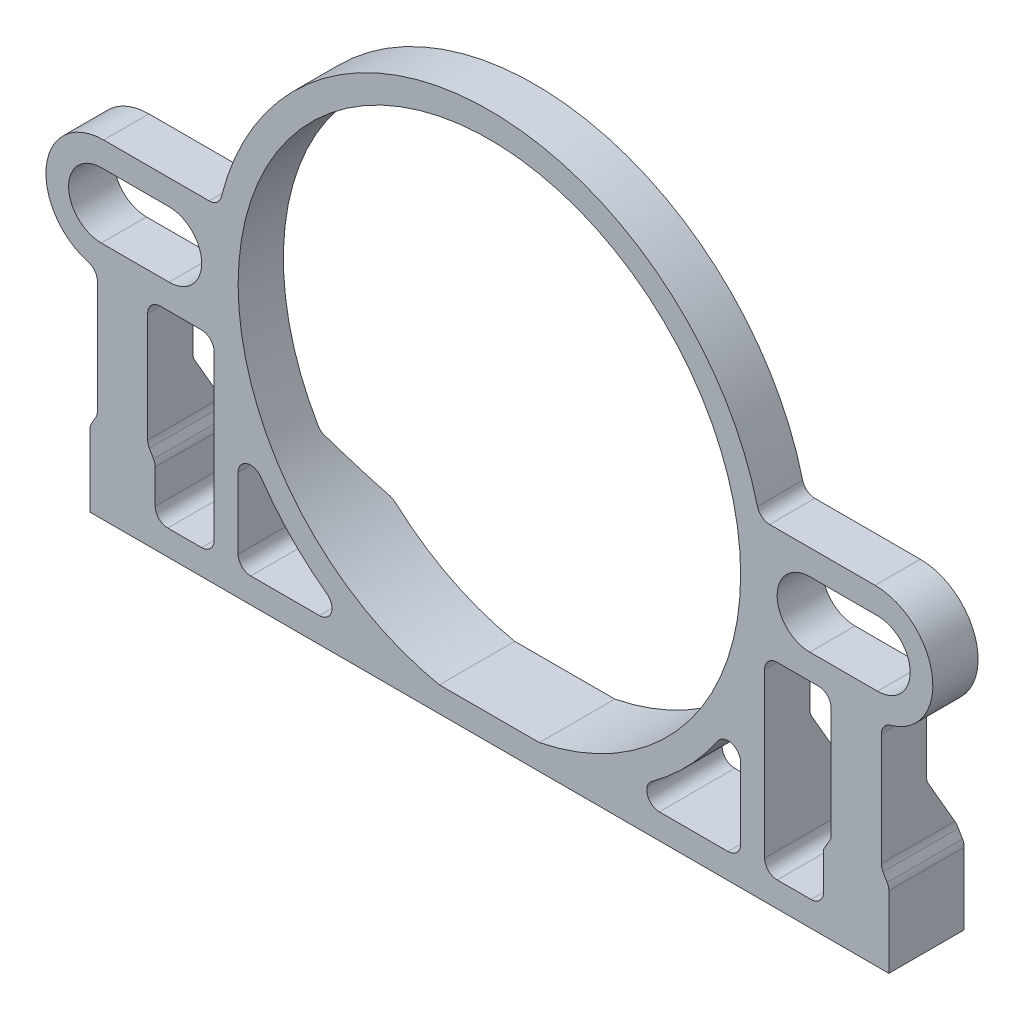
SolidWorks part; units mm, degrees
ref_plane "前视基准面" through (0, 0, 0) normal (0, 0, 1) x (1, 0, 0)
ref_plane "上视基准面" through (0, 0, 0) normal (0, 1, 0) x (1, 0, 0)
ref_plane "右视基准面" through (0, 0, 0) normal (1, 0, 0) x (0, 0, -1)
sketch "草图1" plane through (0, 0, 0) normal (0, 0, 1) x (1, 0, 0)
  line L1 (15.6, -6) -> (-15.6, -6)
  line L2 (15.6, -6) -> (15.6, 6)
  line L3 (15.6, 6) -> (-15.6, 6)
  line L4 (-15.6, -6) -> (-15.6, 6)
  line L5 (15.6, -6) -> (-15.6, 6) construction
  line L6 (15.6, 6) -> (-15.6, -6) construction
  point P0 (0, 0)
  dimension "D1" = 31.2
  dimension "D2" = 12
extrude "凸台-拉伸1" add sketch "草图1" along normal blind 3
sketch "草图2" plane through (0, 0, 3) normal (0, 0, 1) x (1, 0, 0)
  line L0 (15.6, 6) -> (-15.6, 6) construction
  line L1 (-13.6, 6) -> (13.6, 6)
  line L2 (-13.6, 6) -> (-13.6, -5)
  line L3 (-13.6, -5) -> (13.6, -5)
  line L4 (13.6, 6) -> (13.6, -5)
  line L5 (-15.6, 6) -> (-15.6, -6) construction
  line L6 (-15.6, -6) -> (15.6, -6) construction
  dimension "D1" = 2
  dimension "D2" = 27.2
  dimension "D3" = 1
extrude "切除-拉伸1" cut sketch "草图2" against normal blind 3
sketch "草图3" plane through (0, 0, 3) normal (0, 0, 1) x (1, 0, 0)
  line L0 (-15.6, -6) -> (15.6, -6) construction
  line L1 (0, 0) -> (0, 50000) construction
  line L2 (-15.6, 6) -> (-15.6, -6) construction
  circle A0 centre (-14.6, 4.8) radius 2.25
  circle A1 centre (14.6, 4.8) radius 2.25
  dimension "D1" = 10.8
  dimension "D2" = 1
extrude "凸台-拉伸2" add sketch "草图3" against normal blind 3
sketch "草图4" plane through (0, 0, 3) normal (0, 0, 1) x (1, 0, 0)
  circle A0 centre (-14.6, 4.8) radius 1.3
  circle A1 centre (14.6, 4.8) radius 1.3
extrude "切除-拉伸2" cut sketch "草图4" against normal blind 3
sketch "草图5" plane through (0, 0, 3) normal (0, 0, 1) x (1, 0, 0)
  line L0 (-15.6, 2.7844) -> (-15.6, -6) construction
  line L1 (-15.6, -6) -> (15.6, -6) construction
  line L2 (0, 0) -> (0, 50000) construction
  circle A0 centre (-14.6, -2) radius 2.25
  circle A1 centre (14.6, -2) radius 2.25
  dimension "D1" = 1
  dimension "D2" = 4
sketch "草图8" plane through (0, 0, 0) normal (0, 0, -1) x (-1, 0, 0)
  line L0 (-14.6, 4.8) -> (14.6, 4.8) construction
  line L1 (-12.5844, 5.8) -> (-10.9545, 5.8)
  line L2 (-12.5844, 3.8) -> (-10.9545, 3.8)
  line L3 (-10.9545, 3.8) -> (-9.9499, 3.8)
  line L4 (0, 4.8) -> (0, 50004.8) construction
  line L5 (10.9545, 3.8) -> (9.9499, 3.8)
  line L6 (12.5844, 3.8) -> (10.9545, 3.8)
  line L7 (12.5844, 5.8) -> (10.9545, 5.8)
  circle A0 centre (0, 4.8) radius 9 construction
  circle A1 centre (0, 4.8) radius 11 construction
  arc A2 (-13.6, 2.7844) -> (-15.6, 2.7844) centre (-14.6, 4.8) ccw construction
  arc A3 (-10.9545, 5.8) -> (10.9545, 5.8) centre (0, 4.8) cw
  circle A4 centre (0, 4.8) radius 10 construction
  arc A5 (-9.9499, 3.8) -> (9.9499, 3.8) centre (0, 4.8) cw
  arc A6 (-12.5844, 5.8) -> (-12.5844, 3.8) centre (-14.6, 4.8) cw
  arc A7 (12.5844, 5.8) -> (12.5844, 3.8) centre (14.6, 4.8) ccw
  dimension "D1" = 1
  dimension "D2" = 1
extrude "凸台-拉伸5" add sketch "草图8" against normal blind 3
fillet "圆角2" radius 1 6 edges at (-12.5844, 5.8, 1.5) (-10.9545, 5.8, 1.5) (12.5844, 5.8, 1.5) (10.9545, 5.8, 1.5) (-9.9499, 3.8, 1.5) (9.9499, 3.8, 1.5)
sketch "草图9" plane through (0, -6, 0) normal (0, -1, 0) x (-1, 0, 0)
  line L0 (-14.6, 0) -> (14.6, 0) construction
  line L1 (13.5896, -3) -> (15.6104, -3)
  line L3 (16.6207, -1.25) -> (15.6104, 0.5)
  line L4 (15.6104, 0.5) -> (13.5896, 0.5)
  line L5 (13.5896, 0.5) -> (12.5844, -1.2411)
  line L7 (15.6, -3) -> (15.6, 0) construction
  line L8 (-12.5844, -1.2411) -> (-12.5844, -3)
  line L9 (15.6, -3) -> (-15.6, -3) construction
  line L10 (0, 0) -> (0, 7.3942) construction
  line L12 (-13.5896, 0.5) -> (-12.5844, -1.2411)
  line L13 (-15.6104, 0.5) -> (-13.5896, 0.5)
  line L14 (-16.6207, -1.25) -> (-15.6104, 0.5)
  line L16 (-13.5896, -3) -> (-15.6104, -3)
  line L17 (-12.5844, -3) -> (-13.5896, -3)
  line L18 (12.5844, -1.2411) -> (12.5844, -3)
  line L19 (12.5844, -3) -> (13.5896, -3)
  line L20 (-16.6207, -1.25) -> (-16.6207, -3)
  line L21 (12.5793, -1.25) -> (13.5896, -3) [skipped]
  line L22 (-16.85, -3) -> (-12.8265, -3) construction
  line L23 (-16.6207, -3) -> (-15.6104, -3)
  line L24 (16.6207, -1.25) -> (16.6207, -3)
  line L25 (12.8265, -3) -> (16.85, -3) construction
  line L26 (16.6207, -3) -> (15.6104, -3)
  line L28 (15.6104, -3) -> (16.6207, -1.25) [skipped]
  circle A0 centre (14.6, -1.25) radius 1.75 construction
  circle A1 centre (14.6, -1.25) radius 1.05 construction
  circle A2 centre (-14.6, -1.25) radius 1.05 construction
  dimension "D3" = 1.25
  dimension "D1" = 1
  dimension "D2" = 3.5
extrude "凸台-拉伸6" add sketch "草图9" against normal blind 3.5
sketch "草图12" plane through (0, 0, 0) normal (0, 0, -1) x (-1, 0, 0)
  line L0 (-10.9545, 3.8) -> (-10.9545, -5)
  line L1 (13.301, -5) -> (-13.301, -5) construction
  line L2 (-10, 4.8) -> (-10, -5)
  line L3 (-10, -5) -> (-10.9545, -5)
  line L4 (-10.9545, 3.8) -> (-10.9545, 4.8)
  line L5 (-14.6, 4.8) -> (14.6, 4.8) construction
  line L6 (-10.9545, 4.8) -> (-10, 4.8)
  line L7 (0, 4.8) -> (0, 50004.8) construction
  line L9 (10.9545, 3.8) -> (10.9545, 4.8)
  line L10 (10.9545, 3.8) -> (10.9545, -5)
  line L11 (10, -5) -> (10.9545, -5)
  line L12 (10, 4.8) -> (10, -5)
  line L13 (10.9545, 4.8) -> (10, 4.8)
extrude "凸台-拉伸8" add sketch "草图12" against normal blind 3
fillet "圆角3" radius 0.5 10 edges at (10.9545, -5, 1.5) (13.6, 2.7844, 1.5) (12.5844, 3.8, 1.5) (10.9545, 3.801, 1.5) (-13.6, 2.7844, 1.5) (-12.5844, 3.8, 1.5) (-10.9545, 3.801, 1.5) (-10.9545, -5, 1.5) (-10, -5, 1.5) (10, -5, 1.5)
sketch "草图13" plane through (0, 0, 0) normal (0, 0, -1) x (-1, 0, 0)
  line L0 (-10, -4.5) -> (-10, 4.8) construction
  line L1 (9.5, -5) -> (-9.5, -5) construction
  line L2 (-4.9565, -5.02) -> (-1.8886, -5.02)
  line L3 (1.99, -5) -> (4.996, -5)
  line L4 (10, 0.2174) -> (10, 4.8)
  line L5 (-10, 4.8) -> (-10, 0.2174)
  arc A0 (-10, 0.2174) -> (-4.9565, -5.02) centre (0, 4.8) ccw
  circle A1 centre (0, 4.8) radius 11 construction
  arc A2 (-1.8886, -5.02) -> (-10, 4.8) centre (0, 4.8) cw
  circle A3 centre (0, 4.8) radius 10 construction
  arc A4 (9.9499, 3.8) -> (-9.9499, 3.8) centre (0, 4.8) ccw construction
  arc A5 (1.99, -5) -> (10, 4.8) centre (0, 4.8) ccw
  arc A6 (10, 0.2174) -> (4.996, -5) centre (0, 4.8) cw
extrude "凸台-拉伸9" add sketch "草图13" against normal blind 3
fillet "圆角4" radius 0.5 4 edges at (-10, 0.2174, 1.5) (-4.996, -5, 1.5) (4.996, -5, 1.5) (10, 0.2174, 1.5)
sketch "草图14" plane through (0, -2.5, 0) normal (0, 1, 0) x (1, 0, 0)
  line L0 (0, 0) -> (0, 50000) construction
  line L1 (-15.6104, 0.5) -> (-16.6207, -1.25)
  line L2 (-16.6207, -1.25) -> (-15.6104, -3)
  line L3 (-15.6104, -3) -> (-13.5896, -3)
  line L4 (-13.5896, -3) -> (-12.5793, -1.25)
  line L5 (-12.5793, -1.25) -> (-13.5896, 0.5)
  line L6 (-13.5896, 0.5) -> (-15.6104, 0.5)
  line L13 (-16.6207, -1.25) -> (-15.6104, 0.5) construction
  line L14 (-15.6, -3) -> (-15.6104, -3) construction
  line L15 (-13.5896, 0.5) -> (-12.5844, -1.2411) construction
  line L16 (13.5896, 0.5) -> (15.6104, 0.5)
  line L17 (12.5793, -1.25) -> (13.5896, 0.5)
  line L18 (13.5896, -3) -> (12.5793, -1.25)
  line L19 (15.6104, -3) -> (13.5896, -3)
  line L20 (16.6207, -1.25) -> (15.6104, -3)
  line L21 (15.6104, 0.5) -> (16.6207, -1.25)
  circle A0 centre (-14.6, -1.25) radius 1.75 construction
extrude "凸台-拉伸10" add sketch "草图14" against normal blind 0.3 contours L18 L17 L16 L21 L20 L19 | L1 L2 L3 L4 L5 L6
sketch "草图15" plane through (0, -6, 0) normal (0, -1, 0) x (-1, 0, 0)
  line L2 (16.6207, -3) -> (-16.6207, -3) construction
  line L3 (-16.6207, -1.25) -> (-16.6207, -3) construction
  line L5 (16.6207, -3) -> (16.6207, -1.25) construction
  circle A0 centre (14.6, -1.5) radius 0.8
  circle A1 centre (-14.6, -1.5) radius 0.8
  point P6 (0, 0)
  point P9 (0, 0)
  dimension "D1" = 1.5
  dimension "D2" = 1.5
  dimension "D3" = 29.2
  dimension "D4" = 2.0207
  dimension "D5" = 2.0207
extrude "切除-拉伸4" cut sketch "草图15" against normal blind 3.2
sketch "草图16" plane through (0, 0, 3) normal (0, 0, 1) x (1, 0, 0)
  line L0 (-15.6, 4.8) -> (-50015.6, 4.8) construction
  line L3 (-15.35, 4.8) -> (-12.85, 4.8) construction
  line L4 (-15.35, 7.1) -> (-12.85, 7.1)
  line L5 (-15.35, 2.5) -> (-12.85, 2.5)
  line L6 (-12.7524, 4.8) -> (-15.4476, 4.8) construction
  line L7 (-12.7524, 3.5) -> (-15.4476, 3.5)
  line L8 (-12.7524, 6.1) -> (-15.4476, 6.1)
  line L9 (0, 0) -> (0, 50000) construction
  line L10 (15.35, 4.8) -> (12.85, 4.8) construction
  line L11 (15.35, 7.1) -> (12.85, 7.1)
  line L12 (15.35, 2.5) -> (12.85, 2.5)
  line L13 (12.7524, 4.8) -> (15.4476, 4.8) construction
  line L14 (12.7524, 3.5) -> (15.4476, 3.5)
  line L15 (12.7524, 6.1) -> (15.4476, 6.1)
  arc A0 (-12.8265, 6.1846) -> (-12.0383, 5.8) centre (-12.0383, 6.8) ccw construction
  arc A3 (-15.35, 7.1) -> (-15.35, 2.5) centre (-15.35, 4.8) ccw
  arc A4 (-12.85, 2.5) -> (-12.85, 7.1) centre (-12.85, 4.8) ccw
  arc A5 (-12.7524, 3.5) -> (-12.7524, 6.1) centre (-12.7524, 4.8) ccw
  arc A6 (-15.4476, 6.1) -> (-15.4476, 3.5) centre (-15.4476, 4.8) ccw
  circle A7 centre (-14.6, 4.8) radius 1.3 construction
  arc A8 (15.35, 7.1) -> (15.35, 2.5) centre (15.35, 4.8) cw
  arc A9 (12.85, 2.5) -> (12.85, 7.1) centre (12.85, 4.8) cw
  arc A10 (12.7524, 3.5) -> (12.7524, 6.1) centre (12.7524, 4.8) cw
  arc A11 (15.4476, 6.1) -> (15.4476, 3.5) centre (15.4476, 4.8) cw
  point P6 (14.1, 4.8)
  point P12 (-14.1, 4.8)
  point P18 (-14.1, 4.8)
  point P33 (14.1, 4.8)
  dimension "D1" = 0.5
  dimension "D2" = 1.25
  dimension "D3" = 1.3
  dimension "D4" = 1
  dimension "D5" = 0.5
extrude "凸台-拉伸11" add sketch "草图16" against normal blind 3
sketch "草图18" plane through (0, 0, 3) normal (0, 0, 1) x (1, 0, 0)
  line L0 (-12.7524, 4.8) -> (-15.4476, 4.8) construction
  line L1 (-12.7524, 3.5) -> (-15.4476, 3.5)
  line L2 (-12.7524, 6.1) -> (-15.4476, 6.1)
  line L3 (0, 0) -> (0, 50000) construction
  line L4 (12.7524, 4.8) -> (15.4476, 4.8) construction
  line L5 (12.7524, 3.5) -> (15.4476, 3.5)
  line L6 (12.7524, 6.1) -> (15.4476, 6.1)
  arc A0 (-12.7524, 3.5) -> (-12.7524, 6.1) centre (-12.7524, 4.8) ccw
  arc A1 (-15.4476, 6.1) -> (-15.4476, 3.5) centre (-15.4476, 4.8) ccw
  arc A2 (12.7524, 3.5) -> (12.7524, 6.1) centre (12.7524, 4.8) cw
  arc A3 (15.4476, 6.1) -> (15.4476, 3.5) centre (15.4476, 4.8) cw
  point P2 (-14.1, 4.8)
  point P14 (14.1, 4.8)
extrude "切除-拉伸5" cut sketch "草图18" against normal blind 3
sketch "草图19" plane through (0, 0, 3) normal (0, 0, 1) x (1, 0, 0)
  line L0 (-12.85, 7.1) -> (-10.7569, 7.1)
  line L1 (-10.7569, 7.1) -> (-10.7569, 5.8825)
  line L2 (-10.7569, 5.8825) -> (-12.85, 7.1)
  line L3 (-12.85, 2.5) -> (-10.3597, 2.5)
  line L4 (-10.3597, 2.5) -> (-10.8241, 4.2307)
  line L5 (-10.8241, 4.2307) -> (-12.85, 2.5)
  line L6 (12.85, 7.1) -> (10.4542, 7.1)
  line L7 (10.4542, 7.1) -> (10.9022, 5.6877)
  line L8 (10.9022, 5.6877) -> (12.85, 7.1)
  line L9 (12.85, 2.5) -> (10.5662, 2.5)
  line L10 (10.5662, 2.5) -> (10.9022, 4.1339)
  line L11 (10.9022, 4.1339) -> (12.85, 2.5)
  arc A0 (10.8461, 6.6333) -> (-10.8461, 6.6333) centre (0, 4.8) ccw construction
extrude "凸台-拉伸12" add sketch "草图19" against normal blind 3
fillet "圆角7" radius 0.5 8 edges at (10.7569, 7.1, 1.5) (15.6, 2.5136, 1.5) (10.9545, 2.5, 1.5) (13.6, 2.5, 1.5) (-10.7569, 7.1, 1.5) (-15.6, 2.5136, 1.5) (-13.6, 2.5, 1.5) (-10.9545, 2.5, 1.5)
sketch "草图24" plane through (0, -6, 0) normal (0, -1, 0) x (1, 0, 0)
  line L1 (-15.6104, 3) -> (-16.6207, 1.25) construction
  line L2 (-15.899, 2.5) -> (-15.899, 0)
  line L3 (11.99, 0) -> (-11.99, 0) construction
  line L4 (-16.6207, 1.25) -> (-15.6104, -0.5) construction
  line L5 (-15.899, 0) -> (-13.1566, 0)
  line L6 (-13.1566, 0) -> (-13.1566, -0.982)
  line L7 (-13.1566, -0.982) -> (-16.7863, -0.982)
  line L8 (-16.7863, -0.982) -> (-16.7863, 3.1309)
  line L10 (-13.301, 3.6309) -> (-13.301, 2.5) construction
  line L11 (0, 0) -> (0, 6.1692) construction
  line L14 (16.7863, -0.982) -> (16.7863, 3.1309)
  line L15 (13.1566, -0.982) -> (16.7863, -0.982)
  line L16 (13.1566, 0) -> (13.1566, -0.982)
  line L17 (15.899, 0) -> (13.1566, 0)
  line L18 (15.899, 2.5) -> (15.899, 0)
  line L24 (15.899, 2.5) -> (15.899, 3.1309)
  line L25 (15.899, 3.1309) -> (16.7863, 3.1309)
  line L26 (-15.899, 2.5) -> (-15.899, 3.1309)
  line L27 (-15.899, 3.1309) -> (-16.7863, 3.1309)
extrude "切除-拉伸6" cut sketch "草图24" against normal blind 4
sketch "草图25" plane through (0, -2.5, 0) normal (0, 1, 0) x (1, 0, 0)
  line L0 (13.301, 0) -> (13.301, -2.5)
  line L2 (12.5793, -1.25) -> (13.301, 0)
  line L3 (0, 0) -> (0, 9.9869) construction
  line L5 (-13.301, 0) -> (-13.301, -2.5)
  line L6 (-12.5793, -1.25) -> (-13.301, 0)
  line L7 (-12.5793, -1.25) -> (-12.5844, -3)
  line L8 (-12.5844, -3) -> (-13.301, -3)
  line L9 (-12.5844, -3) -> (-13.6, -3) construction
  line L10 (-13.301, -3) -> (-13.301, -2.5)
  line L11 (12.5793, -1.25) -> (12.5844, -3)
  line L12 (13.6, -3) -> (12.5844, -3) construction
  line L13 (12.5844, -3) -> (13.301, -3)
  line L14 (13.301, -3) -> (13.301, -2.5)
extrude "切除-拉伸7" cut sketch "草图25" against normal blind 2.5
fillet "圆角9" radius 0.5 2 edges at (-13.301, -5, 1.5) (13.301, -5, 1.5)
thread "螺纹线7" pitch 0.4 method cut profile "螺纹线轮廓7" start angle 0, offset 0, length 3, pitch 0.4, diameter 1.6
ref_plane "基准面7" through (15.4, -6, 1.5) normal (0, 0, 1) x (1, 0, 0)
sketch "螺纹线轮廓7" plane through (15.4, -6, 1.5) normal (0, 0, 1) x (1, 0, 0)
  line L0 (0, 0) -> (0, 0.4) construction
  line L1 (0, 0) -> (0.2165, 0.125)
  line L2 (0.2165, 0.125) -> (0.2165, 0.175)
  line L3 (0.2165, 0.175) -> (0, 0.3)
  line L4 (0.2165, 0.15) -> (0, 0.15) construction
  line L11 (0, 0) -> (0, 0.3)
  point P2 (0, 0)
  dimension "Pitch" = 0.4
  dimension "Profile_Angle" = 60
  dimension "Profile_Land" = 0.05
  dimension "Profile_Height" = 0.2165
thread "螺纹线8" pitch 0.4 method cut profile "螺纹线轮廓8" start angle 0, offset 0, length 3, pitch 0.4, diameter 1.6
ref_plane "基准面8" through (-13.8, -6, 1.5) normal (0, 0, 1) x (1, 0, 0)
sketch "螺纹线轮廓8" plane through (-13.8, -6, 1.5) normal (0, 0, 1) x (1, 0, 0)
  line L0 (0, 0) -> (0, 0.4) construction
  line L1 (0, 0) -> (0.2165, 0.125)
  line L2 (0.2165, 0.125) -> (0.2165, 0.175)
  line L3 (0.2165, 0.175) -> (0, 0.3)
  line L4 (0.2165, 0.15) -> (0, 0.15) construction
  line L11 (0, 0) -> (0, 0.3)
  point P2 (0, 0)
  dimension "Pitch" = 0.4
  dimension "Profile_Angle" = 60
  dimension "Profile_Land" = 0.05
  dimension "Profile_Height" = 0.2165
sketch "草图30" plane through (0, 0, 3) normal (0, 0, 1) x (1, 0, 0)
  line L0 (-13.6, -2.5) -> (-13.301, -2.5)
  line L1 (-13.301, -2.5) -> (-13.301, -3.0179)
  line L2 (-13.301, -2.5) -> (-13.301, -4.5) construction
  line L3 (-13.301, -3.0179) -> (-13.6, -2.5)
  line L4 (-15.899, -2.5) -> (-15.899, -3.0179)
  line L5 (-15.899, -2.5) -> (-15.899, -6) construction
  line L6 (-15.899, -3.0179) -> (-15.6, -2.5)
  line L7 (-15.6, -2.5) -> (-15.899, -2.5)
  line L8 (0, 0) -> (0, 50000) construction
  line L9 (15.899, -3.0179) -> (15.6, -2.5)
  line L10 (15.899, -2.5) -> (15.899, -3.0179)
  line L11 (15.6, -2.5) -> (15.899, -2.5)
  line L12 (13.301, -2.5) -> (13.301, -3.0179)
  line L13 (13.6, -2.5) -> (13.301, -2.5)
  line L14 (13.301, -3.0179) -> (13.6, -2.5)
  dimension "D1" = 30
  dimension "D2" = 30
extrude "切除-拉伸8" cut sketch "草图30" against normal through all
sketch "草图31" plane through (-15.6, 0, 0) normal (-1, 0, 0) x (0, 0, 1)
  line L0 (0, -2.5) -> (1.2, -0.4215)
  line L1 (1.2, -0.4215) -> (1.2, 19.0201)
  line L2 (1.2, 19.0201) -> (0, 19.0201)
  line L3 (0, 19.0201) -> (0, -2.5)
  dimension "D1" = 30
  dimension "D2" = 1.2
extrude "切除-拉伸9" cut sketch "草图31" against normal mid plane 500
fillet "圆角10" radius 0.5 16 edges at (15.899, -3.0179, 1.5) (15.6, -2.5, 1.5) (-13.6, -2.5, 1.5) (-13.301, -3.0179, 1.5) (-15.899, -3.0179, 1.5) (-15.6, -2.5, 1.5) (-14.6, -2.5, 0) (-14.6, -0.4215, 1.2) (-7.5315, -2.5, 0) (-10.4772, -2.5, 0) (-9.7415, -0.4215, 1.2) (7.5315, -2.5, 0) (14.6, -2.5, 0) (10.4772, -2.5, 0) (9.7415, -0.4215, 1.2) (14.6, -0.4215, 1.2)
